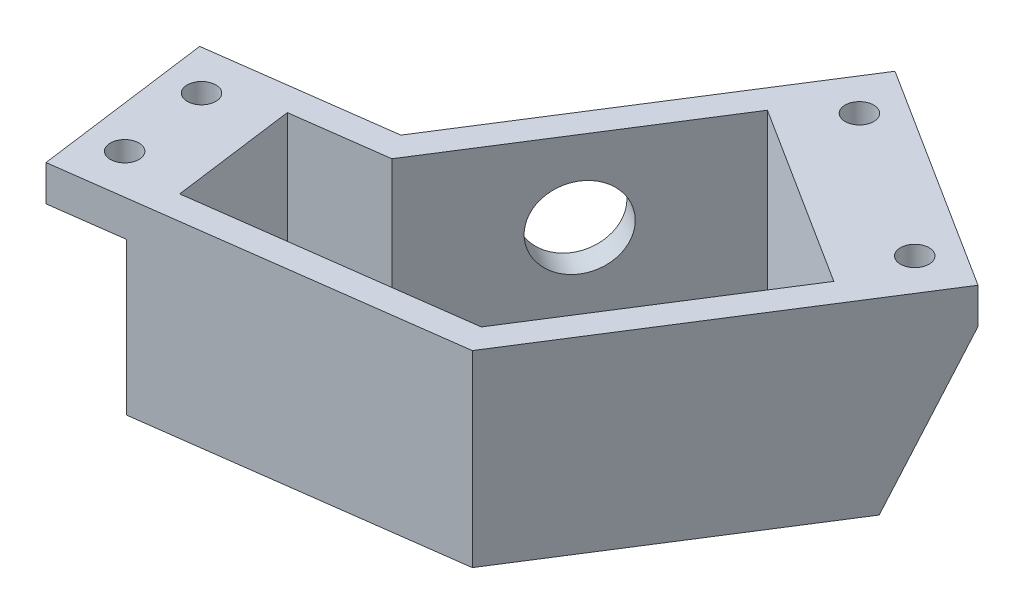
SolidWorks part; units mm, degrees
ref_plane "Спереди" through (0, 0, 0) normal (0, 0, 1) x (1, 0, 0)
ref_plane "Сверху" through (0, 0, 0) normal (0, 1, 0) x (1, 0, 0)
ref_plane "Справа" through (0, 0, 0) normal (1, 0, 0) x (0, 0, -1)
sketch "Sketch1" plane through (0, 0, 0) normal (0, 1, 0) x (1, 0, 0)
  line L0 (0, 0) -> (-19.8234, -2.6518)
  line L1 (-19.8234, -2.6518) -> (-17.1716, -22.4752)
  line L2 (-17.1716, -22.4752) -> (24.8344, -16.856)
  line L3 (24.8344, -16.856) -> (46.7569, 17.7141)
  line L4 (46.7569, 17.7141) -> (21.4217, 33.7803)
  line L5 (21.4217, 33.7803) -> (0, 0)
  line L6 (0, 0) -> (2.6518, -19.8234) construction
  dimension "D1" = 130
  dimension "D2" = 20
  dimension "D3" = 20
  dimension "D4" = 30
  dimension "D5" = 90
  dimension "D6" = 40
extrude "Boss-Extrude1" add sketch "Sketch1" along normal blind 21
sketch "Sketch2" plane through (0, 21, 0) normal (0, 1, 0) x (1, 0, 0)
  line L0 (21.4217, 33.7803) -> (17.1373, 27.0243)
  line L1 (21.4217, 33.7803) -> (0, 0) construction
  line L2 (17.1373, 27.0243) -> (42.4726, 10.958)
  line L3 (24.8344, -16.856) -> (46.7569, 17.7141) construction
  line L4 (42.4726, 10.958) -> (46.7569, 17.7141)
  line L5 (46.7569, 17.7141) -> (21.4217, 33.7803)
  line L6 (-19.8234, -2.6518) -> (-17.1716, -22.4752)
  line L7 (-17.1716, -22.4752) -> (-9.2422, -21.4145)
  line L8 (-17.1716, -22.4752) -> (24.8344, -16.856) construction
  line L9 (-9.2422, -21.4145) -> (-11.8941, -1.5911)
  line L10 (0, 0) -> (-19.8234, -2.6518) construction
  line L11 (-11.8941, -1.5911) -> (-19.8234, -2.6518)
  dimension "D1" = 8
extrude "Cut-Extrude1" cut sketch "Sketch2" along normal offset from surface (17 mm away) 4 from surface up to face at (9.3363, 21, -1.5852) starting at face at (9.3363, 0, -1.5852)
sketch "Sketch3" plane through (0, 21, 0) normal (0, 1, 0) x (1, 0, 0)
  line L0 (18.0642, 22.8841) -> (1.7843, -2.788)
  line L1 (1.7843, -2.788) -> (-8.5228, -4.1668)
  line L2 (-8.5228, -4.1668) -> (-6.6665, -18.0432)
  line L3 (-6.6665, -18.0432) -> (23.0501, -14.068)
  line L4 (23.0501, -14.068) -> (38.3324, 10.0311)
  line L5 (38.3324, 10.0311) -> (18.0642, 22.8841)
  line L6 (18.0642, 22.8841) -> (17.864, 23.073)
  line L7 (21.4217, 33.7803) -> (0, 0) construction
  line L9 (0, 0) -> (-19.8234, -2.6518) construction
  line L10 (-9.2422, -21.4145) -> (-11.8941, -1.5911) construction
  line L11 (-17.1716, -22.4752) -> (24.8344, -16.856) construction
  line L12 (24.8344, -16.856) -> (46.7569, 17.7141) construction
  line L13 (17.1373, 27.0243) -> (42.4726, 10.958) construction
  dimension "D1" = 3
  dimension "D2" = 3
  dimension "D3" = 3
  dimension "D4" = 3
  dimension "D5" = 3
  dimension "D6" = 3
extrude "Cut-Extrude2" cut sketch "Sketch3" against normal offset from surface (18 mm away) 3 contours L4 L5 L0 L1 L2 L3 region at (15.3861, 21, 0.1653) up to face at (10.5514, 0, 0.3132)
sketch "Sketch4" plane through (2.5335, 0, 1.6066) normal (0.8445, 0, 0.5355) x (0.5355, 0, -0.8445)
  line L0 (13.8005, 3) -> (13.8005, 21) construction
  line L3 (29, 21) -> (-1.3989, 21) construction
  line L4 (3.3005, 4) -> (24.3005, 4) construction
  line L5 (3.3005, 4) -> (3.3005, 20) construction
  line L6 (3.3005, 20) -> (24.3005, 20) construction
  line L7 (24.3005, 4) -> (24.3005, 20) construction
  line L8 (3.3005, 4) -> (24.3005, 20) construction
  line L9 (3.3005, 20) -> (24.3005, 4) construction
  line L11 (29, 3) -> (-1.3989, 3) construction
  circle A0 centre (13.8005, 12) radius 4.5
  point P14 (13.8005, 21)
  dimension "D1" = 9
  dimension "D2" = 16
  dimension "D3" = 21
extrude "Cut-Extrude3" cut sketch "Sketch4" against normal through all
sketch "Sketch5" plane through (0, 17, 0) normal (0, -1, 0) x (-1, 0, 0)
  line L0 (-19.2795, 30.4023) -> (-44.6148, 14.3361) construction
  line L1 (-21.4217, 33.7803) -> (-17.1373, 27.0243) construction
  line L2 (-42.4726, 10.958) -> (-46.7569, 17.7141) construction
  line L3 (15.8587, -2.1215) -> (13.2069, -21.9449) construction
  line L4 (11.8941, -1.5911) -> (19.8234, -2.6518) construction
  line L5 (17.1716, -22.4752) -> (9.2422, -21.4145) construction
  circle A0 centre (-40.3922, 17.0138) radius 1.6
  circle A1 centre (-23.5021, 27.7246) radius 1.6
  circle A2 centre (13.8699, -16.989) radius 1.6
  circle A3 centre (15.1958, -7.0773) radius 1.6
  point P20 (14.5328, -12.0332)
  point P21 (-31.9471, 22.3692)
  dimension "D1" = 3.2
  dimension "D2" = 10
  dimension "D3" = 5
  dimension "D4" = 20
  dimension "D5" = 10
extrude "Cut-Extrude4" cut sketch "Sketch5" against normal through all
sketch "Sketch6" plane through (0, 0, 0) normal (-0.8445, 0, -0.5355) x (-0.5355, 0, 0.8445)
  line L0 (-24, 0) -> (-24, 21) construction
  line L1 (-32, 0) -> (0, 0) construction
  line L2 (-40, 21) -> (0, 21) construction
  line L3 (-32, 17) -> (-32, 0) construction
  text T0 "<b>      OBS</b>" font "Arial" height 3
  dimension "D1" = 8
extrude "Cut-Extrude5" cut sketch "Sketch6" against normal blind 0.5
sketch "Sketch7" plane through (-8.9205, 0, 1.1933) normal (0.9912, 0, -0.1326) x (-0.1326, 0, -0.9912)
  line L0 (-10, 3) -> (-10, 21) construction
  line L1 (-3, 3) -> (-17, 3) construction
  line L2 (-3, 21) -> (-17, 21) construction
  circle A0 centre (-10, 10) radius 3
  point P8 (0, 0)
  point P9 (-8.8441, 9.7495)
  point P10 (0, 0)
  dimension "D1" = 6
  dimension "D2" = 11
extrude "Cut-Extrude6" cut sketch "Sketch7" against normal through all
sketch "Sketch8" plane through (0, 0, 0) normal (-0.8445, 0, -0.5355) x (-0.5355, 0, 0.8445)
  line L0 (-32, 0) -> (-40, 17)
  line L1 (-40, 17) -> (-32, 17)
  line L2 (-32, 17) -> (-32, 0)
extrude "Boss-Extrude2" add sketch "Sketch8" against normal up to surface (30 mm away) up to face at (38.0213, 12.6667, -3.9387)
sketch "Sketch9" plane through (0, 21, 0) normal (0, 1, 0) x (1, 0, 0)
  circle A0 centre (23.5021, 27.7246) radius 1.6
  circle A1 centre (40.3922, 17.0138) radius 1.6
extrude "Cut-Extrude7" cut sketch "Sketch9" against normal through all
sketch "Sketch10" plane through (0, 21, 0) normal (0, 1, 0) x (1, 0, 0)
  circle A0 centre (23.5021, 27.7246) radius 3.5
  circle A1 centre (40.3922, 17.0138) radius 3.5
  dimension "D1" = 7
extrude "Cut-Extrude8" cut sketch "Sketch10" against normal through all from offset 4 offset against normal yes
sketch "Sketch11" plane through (0, 0, 0) normal (-0.1326, 0, -0.9912) x (-0.9912, 0, 0.1326)
  line L0 (7, 0) -> (7, 21) construction
  line L1 (0, 0) -> (12, 0) construction
  line L2 (0, 21) -> (20, 21) construction
  line L3 (12, 17) -> (12, 0) construction
  text T0 "<b>     1 / 2</b>" font "Arial" height 3
  dimension "D1" = 5
extrude "Cut-Extrude9" cut sketch "Sketch11" against normal blind 0.5
